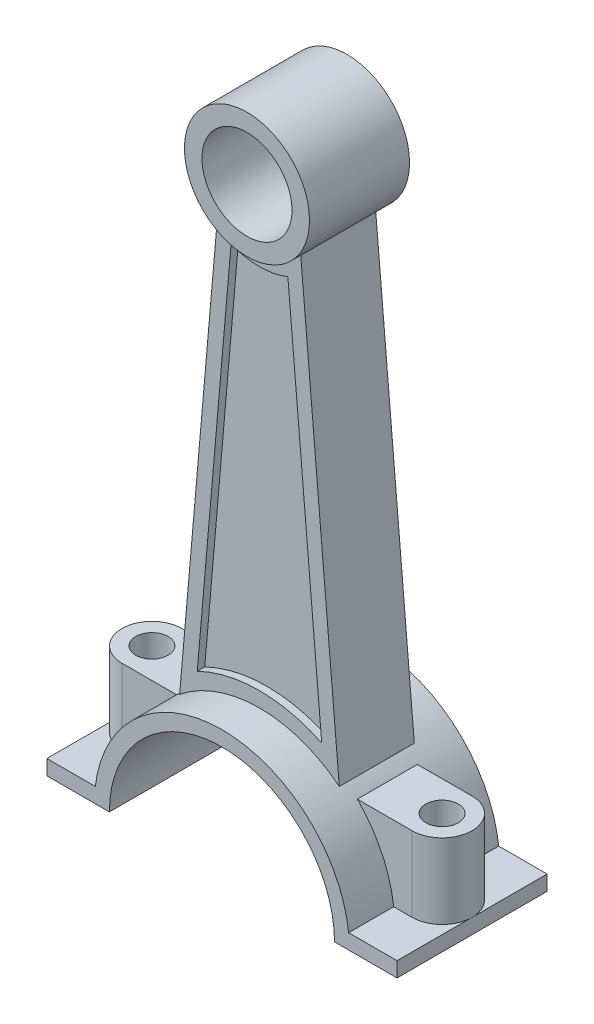
SolidWorks part; units mm, degrees
ref_plane "Front Plane" through (0, 0, 0) normal (0, 0, 1) x (1, 0, 0)
ref_plane "Top Plane" through (0, 0, 0) normal (0, 1, 0) x (1, 0, 0)
ref_plane "Right Plane" through (0, 0, 0) normal (1, 0, 0) x (0, 0, -1)
sketch "Sketch1" plane through (0, 0, 0) normal (0, 0, 1) x (1, 0, 0)
  line L0 (0, 15.5) -> (0, -117.4)
  line L1 (0, -117.4) -> (35, -117.4)
  line L2 (-104.8947, -46.1604) -> (-34.8947, -46.1604)
  line L3 (35, -117.4) -> (35, -99.4)
  line L4 (35, -99.4) -> (18.0624, -99.4)
  line L5 (35, -114.4) -> (25.3229, -114.4)
  line L6 (29, -99.4) -> (29, -117.4)
  line L7 (-15.9574, -97.51) -> (-8.2481, -9.3925)
  line L8 (-29, -99.4) -> (-29, -117.4)
  line L9 (15.9574, -97.51) -> (8.2481, -9.3925)
  line L10 (-35, -114.4) -> (-25.3229, -114.4)
  line L11 (-35, -99.4) -> (-18.0624, -99.4)
  line L12 (-35, -117.4) -> (-35, -99.4)
  line L13 (0, -117.4) -> (-35, -117.4)
  circle A1 centre (0, 0) radius 9
  circle A2 centre (0, 0) radius 12.5
  arc A3 (22.5, -117.4) -> (-22.5, -117.4) centre (0, -117.4) ccw
  arc A5 (25.3229, -114.4) -> (-25.3229, -114.4) centre (0, -117.4) ccw
  dimension "D2" = 25
  dimension "D3" = 18
  dimension "D5" = 12.5
  dimension "D9" = 22.5
  dimension "D10" = 25.5
  dimension "D4" = 132.9
  dimension "D6" = 70
  dimension "D7" = 35
  dimension "D8" = 18
  dimension "D12" = 3
  dimension "D13" = 29
  dimension "D14" = 19.89
  dimension "D15" = 95
extrude "Boss-Extrude3" add sketch "Sketch1" along normal mid plane 30 contours L0 A5 L10 L8 L13 A3 | L5 A5 L0 A3 L1 L6 | L5 L6 L1 L3 | L13 L8 L10 L12 region at (-8.3293, -93.7077, 0) region at (16.7781, -98.7131, 0) region at (-32, -115.9, 0) region at (32, -115.9, 0)
extrude "Boss-Extrude4" add sketch "Sketch1<6>" along normal mid plane 12 contours A5 L11 L8 L10 | L12 L10 L8 L11 | A5 L5 L6 L4 | L4 L6 L5 L3 region at (-25.5197, -105.492, 0) region at (25.5197, -105.492, 0) region at (-32, -106.9, 0) region at (32, -106.9, 0)
sketch "Sketch1<6>" plane through (0, 0, 0) normal (0, 0, 1) x (1, 0, 0) same geometry as "Sketch1"
extrude "Boss-Extrude5" add sketch "Sketch1<7>" along normal mid plane 15 contours A5 L0 A2 L7 | A5 L9 A2 L0 region at (-6.3219, -56.676, 0) region at (6.3219, -56.676, 0)
sketch "Sketch1<7>" plane through (0, 0, 0) normal (0, 0, 1) x (1, 0, 0) same geometry as "Sketch1"
extrude "Boss-Extrude6" add sketch "Sketch1<8>" along normal mid plane 20 contours L0 A2 A1 | L0 A2 A1 region at (8.6412, 8.6412, 0) region at (-0.2795, 10.75, 0)
sketch "Sketch1<8>" plane through (0, 0, 0) normal (0, 0, 1) x (1, 0, 0) same geometry as "Sketch1"
sketch "Sketch3" plane through (0, -99.4, 0) normal (0, 1, 0) x (1, 0, 0)
  line L1 (0, 0) -> (29, 0)
  line L2 (29, 6) -> (35, 6)
  line L3 (35, 6) -> (35, -6)
  line L4 (35, -6) -> (29, -6)
  line L5 (0, 17.763) -> (0, -16.3716) construction
  line L6 (-35, -6) -> (-29, -6)
  line L7 (-35, 6) -> (-35, -6)
  line L8 (-29, 6) -> (-35, 6)
  circle A1 centre (29, 0) radius 6
  circle A2 centre (-29, 0) radius 6
  circle A3 centre (-29, 0) radius 3.25
  circle A4 centre (29, 0) radius 3.25
  line M4 (35, 6) -> (18.0624, 6)
  line M6 (18.0624, -6) -> (35, -6)
  line M7 (35, -6) -> (35, 6)
  dimension "D1" = 29
  dimension "D2" = 6.5
  dimension "D3" = 6.5
extrude "Cut-Extrude2" cut sketch "Sketch3" against normal blind 15 contours L6 A2 L7 | L7 A2 L8 | A1 L3 M4 | A1 M6 M7 region at (33.6598, -99.4, -4.6598) region at (33.6598, -99.4, 4.6598) region at (-33.6598, -99.4, 4.6598) region at (-33.6598, -99.4, -4.6598)
extrude "Cut-Extrude3" cut sketch "Sketch3<7>" against normal through all contours A3 | A4 region at (29, -99.4, -3.1581) region at (-29, -99.4, 0)
sketch "Sketch3<7>" plane through (0, -99.4, 0) normal (0, 1, 0) x (1, 0, 0) same geometry as "Sketch3"
sketch "Sketch4" plane through (0, 0, 7.5) normal (0, 0, 1) x (1, 0, 0)
  line L3 (5.6768, -14.4231) -> (12.4428, -91.7597)
  line L5 (-12.4428, -91.7597) -> (-5.6768, -14.4231)
  arc A0 (-5.6768, -14.4231) -> (5.6768, -14.4231) centre (0, 0) ccw
  arc A3 (17.8347, -95.17) -> (-17.8347, -95.17) centre (0, -117.4) ccw
  arc A4 (12.4428, -91.7597) -> (-12.4428, -91.7597) centre (0, -117.4) ccw
  dimension "D1" = 31
  dimension "D3" = 3
extrude "Cut-Extrude5" cut sketch "Sketch4" against normal blind 1.5
sketch "Sketch6" plane through (0, 0, -7.5) normal (0, 0, -1) x (-1, 0, 0)
  line L0 (5.6768, -14.4231) -> (12.4428, -91.7597)
  line L1 (-12.4428, -91.7597) -> (-5.6768, -14.4231)
  arc A0 (-5.6768, -14.4231) -> (5.6768, -14.4231) centre (0, 0) ccw
  arc A1 (12.4428, -91.7597) -> (-12.4428, -91.7597) centre (0, -117.4) ccw
extrude "Cut-Extrude6" cut sketch "Sketch6" against normal blind 1.5
